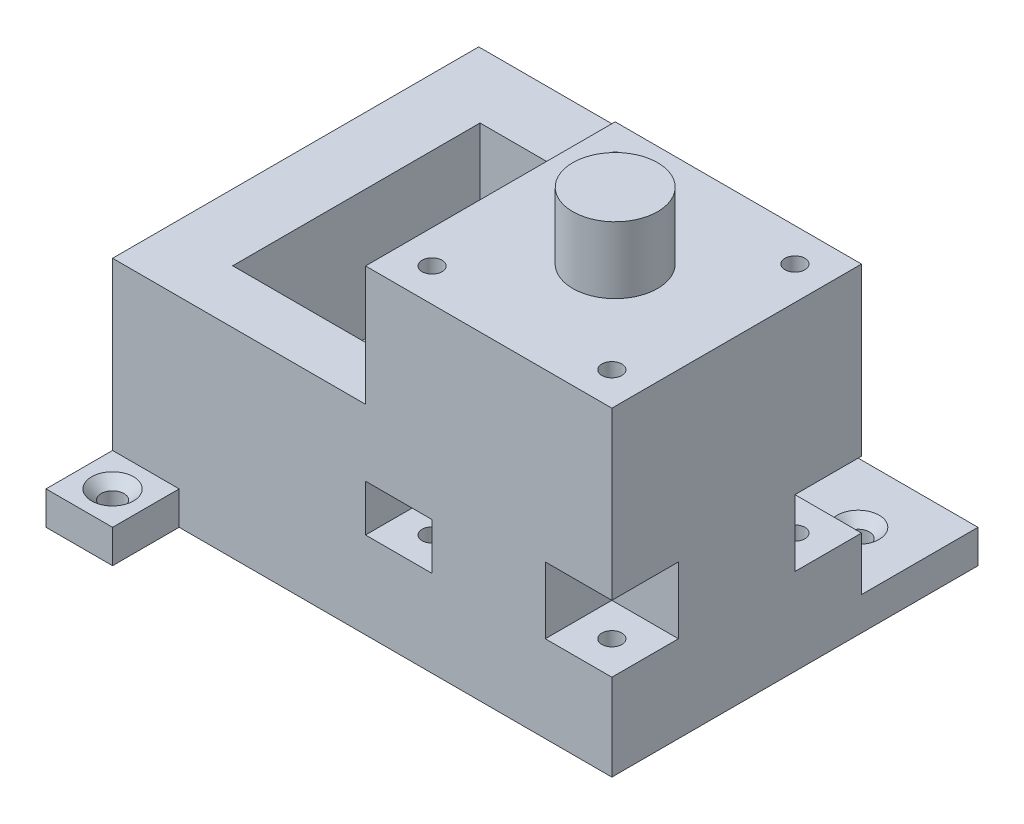
SolidWorks part; units mm, degrees
ref_plane "Plan de face" through (0, 0, 0) normal (0, 0, 1) x (1, 0, 0)
ref_plane "Plan de dessus" through (0, 0, 0) normal (0, 1, 0) x (1, 0, 0)
ref_plane "Plan de droite" through (0, 0, 0) normal (1, 0, 0) x (0, 0, -1)
sketch "Esquisse3" plane through (0, 0, 0) normal (0, 1, 0) x (1, 0, 0)
  line L0 (0, 0) -> (0, 55)
  line L1 (0, 55) -> (38, 55)
  line L2 (38, 55) -> (38, 37.5)
  line L3 (38, 37.5) -> (75, 37.5)
  line L4 (75, 37.5) -> (75, 0)
  line L5 (75, 0) -> (0, 0)
  dimension "D1" = 55
  dimension "D2" = 38
  dimension "D3" = 37.5
  dimension "D4" = 37
  dimension "D5" = 75
extrude "Boss.-Extru.1" add sketch "Esquisse3" along normal blind 30
sketch "Esquisse6" plane through (0, 30, 0) normal (0, 1, 0) x (1, 0, 0)
  line L0 (0, 0) -> (75, 0) construction
  line L1 (75, 37.5) -> (38, 37.5)
  line L2 (75, 37.5) -> (75, 0)
  line L3 (75, 0) -> (38, 0)
  line L4 (38, 37.5) -> (38, 0)
  dimension "D1" = 37
extrude "Boss.-Extru.4" add sketch "Esquisse6" along normal blind 18
sketch "Esquisse7" plane through (0, 48, 0) normal (0, 1, 0) x (1, 0, 0)
  line L0 (75, 37.5) -> (38, 37.5) construction
  line L1 (75, 0) -> (75, 37.5) construction
  circle A0 centre (56.5, 19) radius 6.375
  dimension "D3" = 12.75
  dimension "D1" = 18.5
  dimension "D2" = 18.5
extrude "Boss.-Extru.5" add sketch "Esquisse7" along normal blind 10
sketch "Esquisse8" plane through (0, 48, 0) normal (0, 1, 0) x (1, 0, 0)
  line L0 (75, 0) -> (75, 37.5) construction
  line L2 (75, 37.5) -> (38, 37.5) construction
  line L3 (38, 0) -> (75, 0) construction
  line L4 (38, 37.5) -> (38, 0) construction
  line L5 (38, 37.5) -> (38, 0) construction
  circle A0 centre (43, 32.5) radius 1.5
  circle A1 centre (70, 32.5) radius 1.5
  circle A2 centre (70, 5) radius 1.5
  circle A3 centre (43, 5) radius 1.5
  point P12 (76.0397, 37.5)
  point P15 (-23.7498, 50.9434)
  point P20 (9.9527, 53.6568)
  point P21 (50.2726, 37.5)
  dimension "D2" = 5
  dimension "D9" = 3
  dimension "D10" = 3
  dimension "D11" = 3
  dimension "D12" = 3
  dimension "D1" = 5
  dimension "D3" = 5
  dimension "D4" = 5
  dimension "D5" = 5
  dimension "D6" = 5
  dimension "D7" = 5
  dimension "D8" = 5
extrude "Enlèv. mat.-Extru.1" cut sketch "Esquisse8" against normal blind 43
sketch "Esquisse9" plane through (75, 0, 0) normal (1, 0, 0) x (0, 0, -1)
  line L0 (0, 48) -> (0, 0) construction
  line L1 (0, 13) -> (10, 13)
  line L2 (0, 13) -> (0, 23)
  line L3 (0, 23) -> (10, 23)
  line L4 (10, 13) -> (10, 23)
  line L6 (0, 48) -> (37.5, 48) construction
  line L7 (37.5, 48) -> (37.5, 0) construction
  line L8 (37.5, 13) -> (27.5, 13)
  line L9 (37.5, 13) -> (37.5, 23)
  line L10 (37.5, 23) -> (27.5, 23)
  line L11 (27.5, 13) -> (27.5, 23)
  dimension "D1" = 25
  dimension "D2" = 10
  dimension "D3" = 10
  dimension "D4" = 25
  dimension "D5" = 10
  dimension "D6" = 10
extrude "Enlèv. mat.-Extru.2" cut sketch "Esquisse9" against normal blind 10
sketch "Esquisse10" plane through (0, 0, -37.5) normal (0, 0, -1) x (-1, 0, 0)
  line L0 (-38, 48) -> (-38, 30) construction
  line L1 (-38, 20) -> (-48, 20)
  line L2 (-38, 20) -> (-38, 13)
  line L3 (-38, 13) -> (-48, 13)
  line L4 (-48, 20) -> (-48, 13)
  line L5 (-75, 48) -> (-38, 48) construction
  dimension "D1" = 28
  dimension "D2" = 7
  dimension "D3" = 10
extrude "Enlèv. mat.-Extru.5" cut sketch "Esquisse10" against normal blind 10
sketch "Esquisse11" plane through (0, 0, 0) normal (0, 0, 1) x (1, 0, 0)
  line L0 (38, 48) -> (38, 30) construction
  line L1 (38, 20) -> (48, 20)
  line L2 (38, 20) -> (38, 13)
  line L3 (38, 13) -> (48, 13)
  line L4 (48, 20) -> (48, 13)
  line L5 (38, 48) -> (75, 48) construction
  dimension "D1" = 28
  dimension "D2" = 7
  dimension "D3" = 10
extrude "Enlèv. mat.-Extru.6" cut sketch "Esquisse11" against normal blind 10
sketch "Esquisse12" plane through (0, 30, 0) normal (0, 1, 0) x (1, 0, 0)
  line L0 (75, 0) -> (75, 37.5) construction
  line L1 (10, 45.1988) -> (30, 45.1988)
  line L2 (10, 45.1988) -> (10, 8.0441)
  line L3 (10, 8.0441) -> (30, 8.0441)
  line L4 (30, 45.1988) -> (30, 8.0441)
  dimension "D1" = 45
  dimension "D2" = 20
extrude "Enlèv. mat.-Extru.7" cut sketch "Esquisse12" against normal blind 19.44
sketch "Esquisse13" plane through (0, 0, -45.1988) normal (0, 0, 1) x (1, 0, 0)
  line L0 (30, 10.56) -> (10, 10.56) construction
  line L1 (15, 10.56) -> (25, 10.56)
  line L2 (15, 10.56) -> (15, 20.56)
  line L3 (15, 20.56) -> (25, 20.56)
  line L4 (25, 10.56) -> (25, 20.56)
  dimension "D1" = 5
  dimension "D2" = 5
  dimension "D3" = 10
extrude "Enlèv. mat.-Extru.8" cut sketch "Esquisse13" against normal up to surface (9.8012 mm away) up to face at (19, 15, -55)
sketch "Esquisse14" plane through (0, 0, 0) normal (0, -1, 0) x (1, 0, 0)
  line L0 (38, -55) -> (0, -55) construction
  line L1 (38, -37.5) -> (75, -37.5)
  line L2 (38, -37.5) -> (38, -55)
  line L3 (38, -55) -> (75, -55)
  line L4 (75, -37.5) -> (75, -55)
  line L5 (75, 0) -> (75, -37.5) construction
extrude "Boss.-Extru.6" add sketch "Esquisse14" against normal blind 5
sketch "Esquisse15" plane through (0, 0, 0) normal (0, -1, 0) x (1, 0, 0)
  line L1 (0, 0) -> (10, 0)
  line L2 (0, 0) -> (0, 10)
  line L3 (0, 10) -> (10, 10)
  line L4 (10, 0) -> (10, 10)
  dimension "D1" = 10
  dimension "D2" = 10
sketch "Esquisse20" plane through (0, 0, 0) normal (0, 0, 1) x (1, 0, 0)
  line L1 (0, 0) -> (10, 0)
  line L2 (0, 0) -> (0, 5)
  line L3 (0, 5) -> (10, 5)
  line L4 (10, 0) -> (10, 5)
  dimension "D1" = 5
  dimension "D2" = 10
extrude "Boss.-Extru.8" add sketch "Esquisse20" along normal blind 10
sketch "Esquisse21" plane through (0, 5, 0) normal (0, 1, 0) x (1, 0, 0)
  line L0 (0, 0) -> (38, 0) construction
  line L3 (10, 0) -> (10, -10) construction
  line L4 (38, 55) -> (75, 55) construction
  line L5 (38, 37.5) -> (38, 55) construction
  line L6 (75, 55) -> (75, 37.5) construction
  circle A0 centre (5, -5) radius 1.5
  circle A1 centre (47, 46) radius 1.5
  circle A2 centre (66, 46) radius 1.5
  point P10 (10, -6.2742)
  dimension "D1" = 5
  dimension "D3" = 3
  dimension "D6" = 3
  dimension "D8" = 3
  dimension "D2" = 5
  dimension "D4" = 9
  dimension "D5" = 9
  dimension "D7" = 9
  dimension "D9" = 9
hole_wizard "Fraisage pour vis à tête fraisée bombée M32" positions "Esquisse22" profile "Esquisse23" countersink size "M3" standard "ISO"
sketch "Esquisse22" plane through (0, 5, 0) normal (0, 1, 0) x (1, 0, 0)
  point P0 (5, -5)
  point P3 (47, 46)
  point P6 (66, 46)
sketch "Esquisse23" plane through (5, 5, 5) normal (1, 0, 0) x (0, 0, 1)
  line L0 (0, 0) -> (0, 6.0215)
  line L1 (0, 6.0215) -> (1.7, 5)
  line L2 (1.7, 5) -> (1.7, 1.45)
  line L3 (1.7, 1.45) -> (3.15, 0)
  line L5 (3.15, 0) -> (0, 0)
  line L6 (-1.7, 1.45) -> (-3.15, 0) construction
  line L10 (0, 6.0215) -> (-1.7, 5) construction
  line L11 (0, -6.35) -> (0, 107.95) construction
  dimension "Diamètre du perçage" = 3.4
  dimension "Profondeur du perçage" = 5
  dimension "Diamètre du fraisage entrant" = 6.3
  dimension "Angle du fraisage entrant" = 90
  dimension "Angle de pointe" = 118
